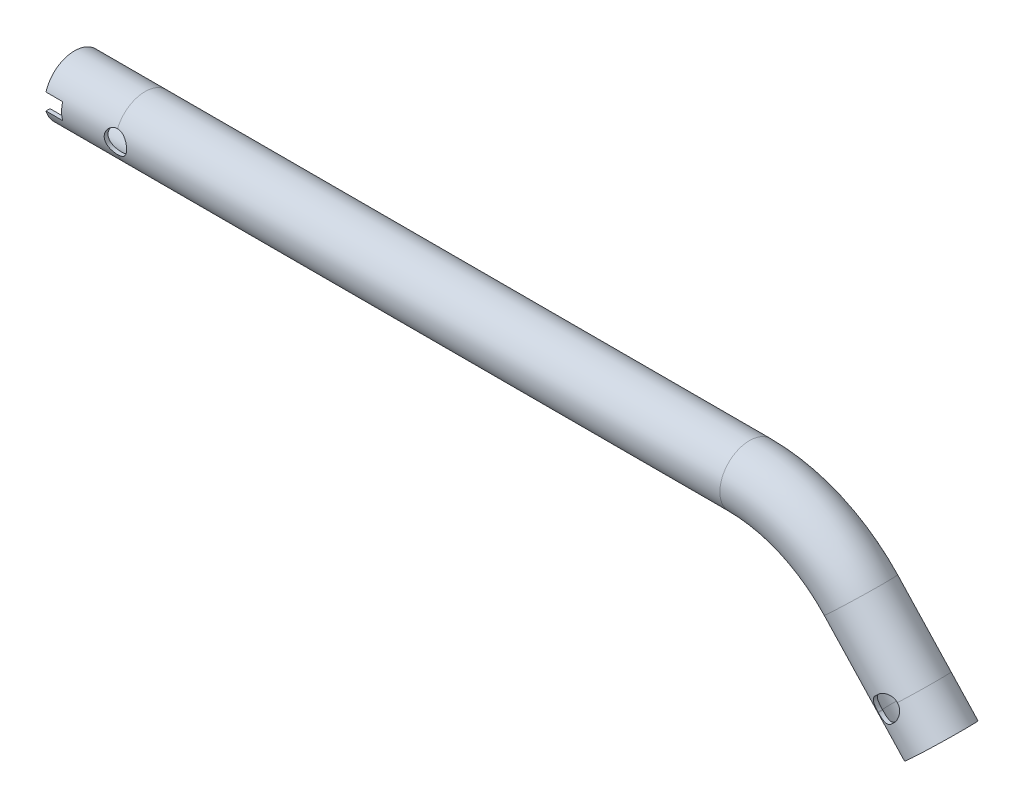
SolidWorks part; units mm, degrees
ref_plane "Front Plane" through (0, 0, 0) normal (0, 0, 1) x (1, 0, 0)
ref_plane "Top Plane" through (0, 0, 0) normal (0, 1, 0) x (1, 0, 0)
ref_plane "Right Plane" through (0, 0, 0) normal (1, 0, 0) x (0, 0, -1)
sketch "Sketch1" plane through (0, 0, 0) normal (0, 0, 1) x (1, 0, 0)
  line L0 (0, 0) -> (188.5734, 0)
  line L1 (223.3127, -15.1051) -> (240, -33)
  line L2 (0, 0) -> (-22.0074, 0)
  line L3 (240, -33) -> (248.3926, -42)
  arc A0 (223.3127, -15.1051) -> (188.5734, 0) centre (188.5734, -47.5) ccw
  point P10 (240, -33)
  dimension "D2" = 47.5
  dimension "D1" = 47
  dimension "D3" = 240
  dimension "D4" = 33
  dimension "D5" = 270.4
  dimension "D6" = 42
ref_plane "Plane1" through (-22.0074, 0, 0) normal (-1, 0, 0) x (0, 0, 1)
sketch "Sketch2" plane through (-22.0074, 0, 0) normal (-1, 0, 0) x (0, 0, 1)
  circle A0 centre (0, 0) radius 9.25
  circle A1 centre (0, 0) radius 8.05
  dimension "D1" = 1.2
  dimension "D2" = 18.5
sweep "Sweep1" add profiles "Sketch2" path "Sketch1"
sketch "Sketch3" plane through (0, 0, 0) normal (0, 0, 1) x (1, 0, 0)
  line L0 (240, -33) -> (242.9986, -30.2038) construction
  line L1 (233.235, -39.3085) -> (246.765, -26.6915) construction
  line L2 (240, -33) -> (237.5789, -30.4037) construction
  line L3 (243.0555, -30.2649) -> (242.9416, -30.1427)
  line L4 (237.9948, -29.97) -> (237.1172, -30.7883)
  line L5 (236.9445, -35.7351) -> (237.0584, -35.8573)
  line L6 (242.0052, -36.03) -> (242.8828, -35.2117)
  arc A0 (242.0052, -36.03) -> (237.0584, -35.8573) centre (239.6182, -33.4703) cw
  arc A1 (242.8828, -35.2117) -> (243.0555, -30.2649) centre (240.4958, -32.6519) ccw
  arc A2 (242.9416, -30.1427) -> (237.9948, -29.97) centre (240.3818, -32.5297) ccw
  arc A3 (237.1172, -30.7883) -> (236.9445, -35.7351) centre (239.5042, -33.3481) ccw
  point P8 (242.9986, -30.2038)
  point P14 (245.4425, -32.8247)
  point P17 (240.5546, -27.583)
  point P20 (234.5575, -33.1753)
  dimension "D6" = 3.5
  dimension "D1" = 4.1
  dimension "D2" = 3.55
  dimension "D3" = 90
  dimension "D4" = 7.1671
  dimension "D5" = 8.2
extrude "Cut-Extrude1" cut sketch "Sketch3" against normal up to next and the other way up to next
sketch "Sketch4" plane through (0, 0, 0) normal (0, 0, 1) x (1, 0, 0)
  line L0 (0, -9.25) -> (0, 9.25) construction
  circle A0 centre (0, 0) radius 3.5
  dimension "D1" = 7
extrude "Cut-Extrude2" cut sketch "Sketch4" along normal up to next
sketch "Sketch5" plane through (0, 0, 0) normal (0, 0, 1) x (1, 0, 0)
  line L0 (-22.0074, 0) -> (-22.0074, 2.555)
  line L1 (-22.0074, 9.25) -> (-22.0074, -9.25) construction
  line L2 (-22.0074, 2.555) -> (-16.8074, 2.555)
  line L3 (-16.8074, 2.555) -> (-16.8074, -2.555)
  line L4 (-16.8074, -2.555) -> (-22.0074, -2.555)
  line L5 (-22.0074, -2.555) -> (-22.0074, 0)
  dimension "D1" = 5.2
  dimension "D2" = 5.11
extrude "Cut-Extrude3" cut sketch "Sketch5" against normal through all and the other way through all
